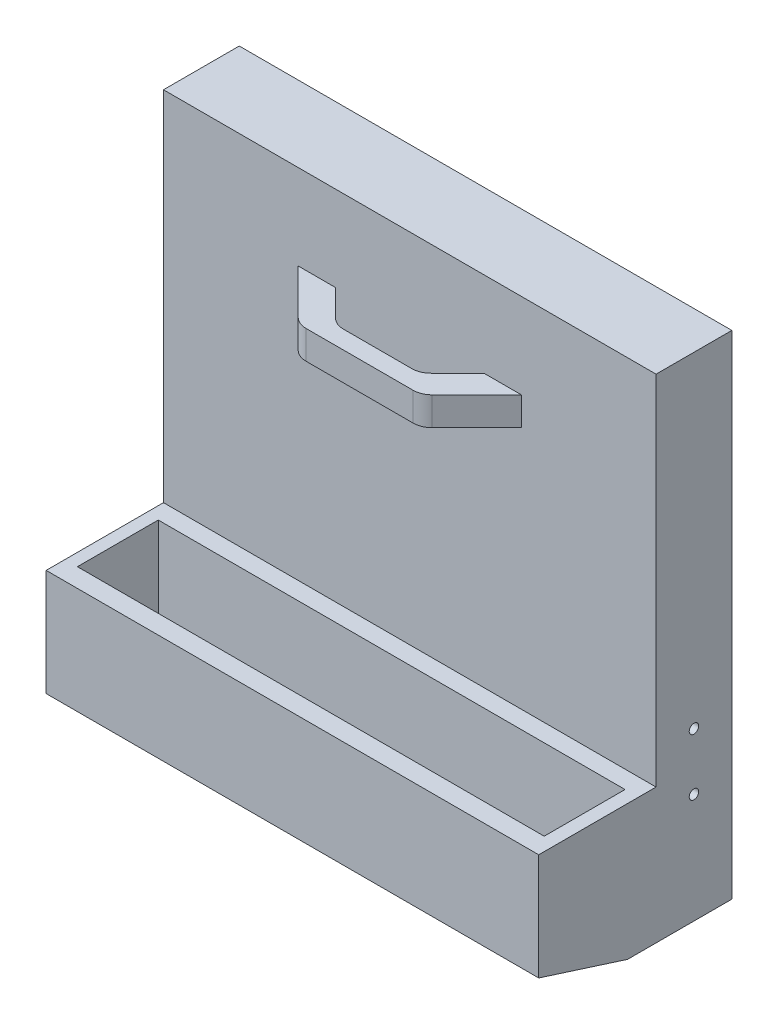
SolidWorks part; units mm, degrees
ref_plane "Front Plane" through (0, 0, 0) normal (0, 0, 1) x (1, 0, 0)
ref_plane "Top Plane" through (0, 0, 0) normal (0, 1, 0) x (1, 0, 0)
ref_plane "Right Plane" through (0, 0, 0) normal (1, 0, 0) x (0, 0, -1)
sketch "Sketch1" plane through (0, 0, 0) normal (0, 0, 1) x (1, 0, 0)
  line L1 (0, 0) -> (330.2, 0)
  line L2 (0, 0) -> (0, 330.2)
  line L3 (0, 330.2) -> (330.2, 330.2)
  line L4 (330.2, 0) -> (330.2, 330.2)
  dimension "D1" = 330.2
  dimension "D2" = 330.2
extrude "Boss-Extrude1" add sketch "Sketch1" along normal blind 50.8
sketch "Sketch2" plane through (0, 0, 0) normal (0, 1, 0) x (1, 0, 0)
  line L1 (0, -50.8) -> (330.2, -50.8) construction
  line L2 (142.1041, -72.3039) -> (188.0959, -72.3039)
  line L3 (197.0762, -68.5842) -> (214.8603, -50.8)
  line L4 (214.8603, -50.8) -> (239.8975, -50.8)
  line L5 (239.8975, -50.8) -> (209.9878, -80.7097)
  line L6 (201.0075, -84.4295) -> (129.1925, -84.4295)
  line L9 (165.1, 11.1319) -> (165.1, -112.7319) construction
  line L10 (90.3025, -50.8) -> (120.2122, -80.7097)
  line L11 (115.3397, -50.8) -> (90.3025, -50.8)
  line L12 (133.1238, -68.5842) -> (115.3397, -50.8)
  arc A0 (188.0959, -72.3039) -> (197.0762, -68.5842) centre (188.0959, -59.6039) ccw
  arc A1 (209.9878, -80.7097) -> (201.0075, -84.4295) centre (201.0075, -71.7295) cw
  arc A2 (120.2122, -80.7097) -> (129.1925, -84.4295) centre (129.1925, -71.7295) ccw
  arc A3 (142.1041, -72.3039) -> (133.1238, -68.5842) centre (142.1041, -59.6039) cw
  point P12 (165.1, -50.8)
  point P21 (165.1, -84.4295)
  point P23 (165.1, -72.3039)
  dimension "D1" = 12.7
  dimension "D2" = 12.7
extrude "Boss-Extrude2" add sketch "Sketch2" along normal blind 19.05 from offset 254
shell "Shell1" thickness 6.35 removed face at (165.1, 165.1, 0)
sketch "Sketch3" plane through (0, 0, 0) normal (-1, 0, 0) x (0, 0, 1)
  circle A0 centre (25.4, 111.6817) radius 3.175
  circle A1 centre (25.4, 73.5817) radius 3.175
  dimension "D1" = 6.35
  dimension "D2" = 6.35
  dimension "D3" = 25.4
  dimension "D4" = 38.1
extrude "Cut-Extrude1" cut sketch "Sketch3" against normal through all
sketch "Sketch4" plane through (0, 0, 0) normal (-1, 0, 0) x (0, 0, 1)
  line L0 (50.8, 0) -> (69.9089, 0)
  line L1 (69.9089, 0) -> (129.4446, 18.9677)
  line L2 (129.4446, 18.9677) -> (129.4446, 90.5053)
  line L3 (129.4446, 90.5053) -> (50.8, 90.5053)
  line L4 (50.8, 90.5053) -> (50.8, 0)
  line L5 (50.8, 330.2) -> (50.8, 0) construction
extrude "Boss-Extrude3" add sketch "Sketch4" against normal up to surface (330.2 mm away) up to face at (330.2, 111.6817, 28.575)
sketch "Sketch5" plane through (0, 90.5053, 0) normal (0, 1, 0) x (1, 0, 0)
  line L1 (8.3379, -116.8331) -> (321.2506, -116.8331)
  line L2 (8.3379, -116.8331) -> (8.3379, -62.6289)
  line L3 (8.3379, -62.6289) -> (321.2506, -62.6289)
  line L4 (321.2506, -116.8331) -> (321.2506, -62.6289)
extrude "Cut-Extrude2" cut sketch "Sketch5" against normal blind 68.58
